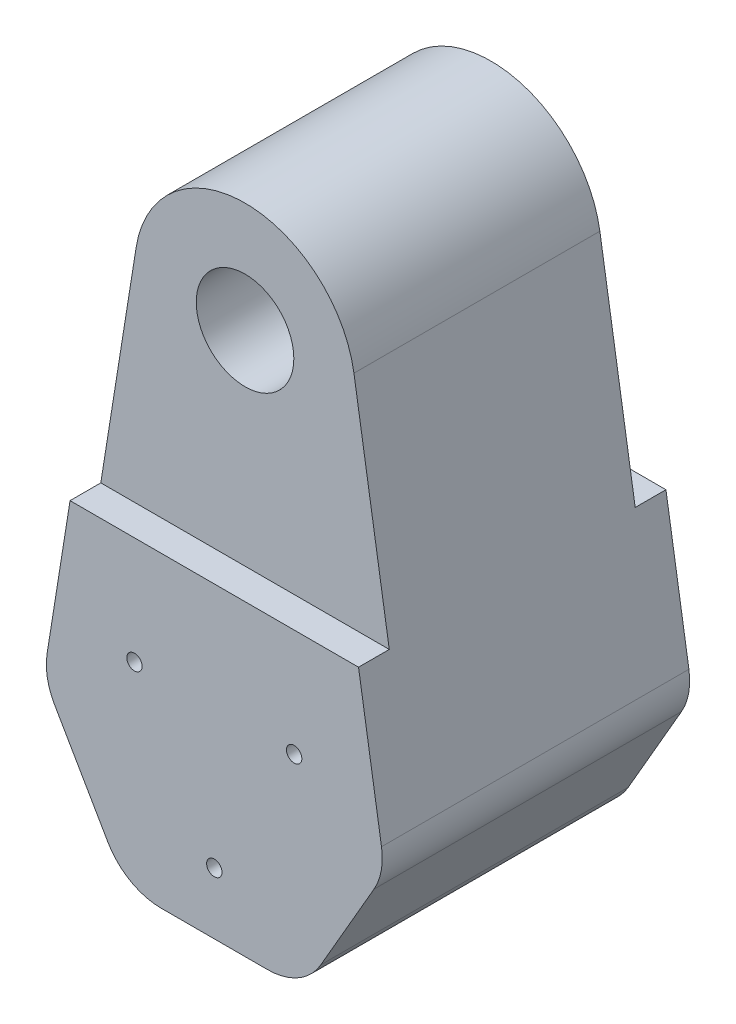
SolidWorks part; units mm, degrees
ref_plane "Front Plane" through (0, 0, 0) normal (0, 0, 1) x (1, 0, 0)
ref_plane "Top Plane" through (0, 0, 0) normal (0, 1, 0) x (1, 0, 0)
ref_plane "Right Plane" through (0, 0, 0) normal (1, 0, 0) x (0, 0, -1)
sketch "Sketch1" plane through (0, 0, 0) normal (0, 0, 1) x (1, 0, 0)
  line L0 (-17.7137, 2.8246) -> (-27.1957, -56.6385)
  line L1 (-25.9808, -63.2132) -> (-17.3205, -78.2132)
  line L2 (-8.6603, -83.2132) -> (8.6603, -83.2132)
  line L3 (17.3205, -78.2132) -> (25.9808, -63.2132)
  line L4 (27.1957, -56.6385) -> (17.7137, 2.8246)
  line L11 (84.0896, -33.2132) -> (-84.0896, -33.2132) construction
  line L12 (-69.5159, -83.2132) -> (69.5159, -83.2132) construction
  line L13 (0, -58.2132) -> (21.6506, -70.7132) construction
  line L14 (-23.4603, -33.2132) -> (23.4603, -33.2132)
  circle A0 centre (0, 0) radius 7.9375
  arc A1 (-17.7137, 2.8246) -> (17.7137, 2.8246) centre (0, 0) cw
  circle A2 centre (0, -58.2132) radius 15 construction
  circle A3 centre (-12.9904, -50.7132) radius 1.25
  circle A4 centre (12.9904, -50.7132) radius 1.25
  circle A5 centre (0, -73.2132) radius 1.25
  arc A8 (25.9808, -63.2132) -> (27.1957, -56.6385) centre (17.3205, -58.2132) ccw
  arc A9 (8.6603, -83.2132) -> (17.3205, -78.2132) centre (8.6603, -73.2132) ccw
  arc A10 (-17.3205, -78.2132) -> (-8.6603, -83.2132) centre (-8.6603, -73.2132) ccw
  arc A11 (-27.1957, -56.6385) -> (-25.9808, -63.2132) centre (-17.3205, -58.2132) ccw
  circle A12 centre (0, -58.2132) radius 15 construction
  circle A13 centre (-12.9904, -50.7132) radius 1.65 construction
  point P11 (0, -83.2132)
  point P20 (0, -58.2132)
  dimension "D1" = 15.875
  dimension "D4" = 2.5
  dimension "D8" = 10
  dimension "D11" = 10
  dimension "D3" = 3
extrude "Boss-Extrude1" add sketch "Sketch1" along normal mid plane 50 contours L0 A11 L1 A10 L2 A9 L3 A8 L4 L14 A3 A4 A5 region at (0, -56.6086, 0)
extrude "Boss-Extrude2" add sketch "Sketch1<3>" along normal mid plane 40 contours A1 L0 L14 L4 A0 region at (0, -11.8814, 0)
sketch "Sketch1<3>" plane through (0, 0, 0) normal (0, 0, 1) x (1, 0, 0) same geometry as "Sketch1"
